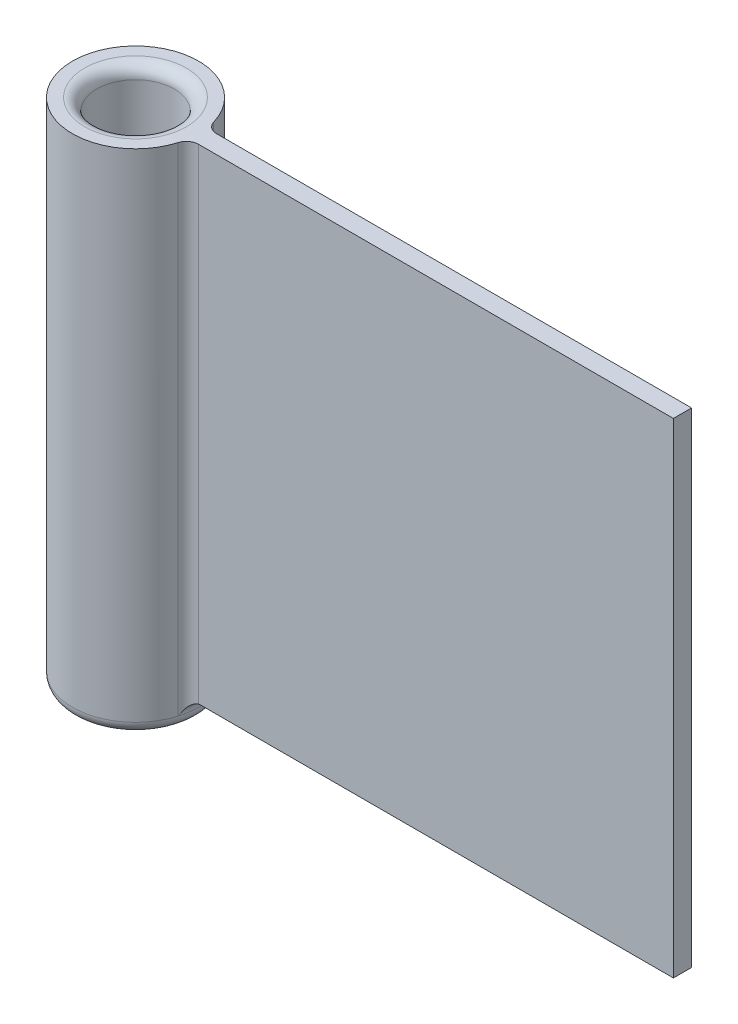
SolidWorks part; units mm, degrees
ref_plane "Front Plane" through (0, 0, 0) normal (0, 0, 1) x (1, 0, 0)
ref_plane "Top Plane" through (0, 0, 0) normal (0, 1, 0) x (1, 0, 0)
ref_plane "Right Plane" through (0, 0, 0) normal (1, 0, 0) x (0, 0, -1)
sketch "Sketch1" plane through (0, 0, 0) normal (0, 1, 0) x (1, 0, 0)
  circle A0 centre (0, 0) radius 3.2
  circle A1 centre (0, 0) radius 5.2
  dimension "D1" = 6.4
  dimension "D2" = 2
extrude "Boss-Extrude1" add sketch "Sketch1" along normal blind 40
sketch "Sketch3" plane through (0, 0, 0) normal (0, 1, 0) x (1, 0, 0)
  line L0 (0, 0) -> (55.2051, 0) construction
  line L1 (45.1456, 0.75) -> (5.1456, 0.75)
  line L2 (45.1456, -0.75) -> (5.1456, -0.75)
  line L3 (45.1456, -0.75) -> (45.1456, 0.75)
  line L4 (5.1456, -0.75) -> (5.1456, 0.75)
  circle A0 centre (0, 0) radius 5.2 construction
  dimension "D1" = 1.5
  dimension "D2" = 40
extrude "Boss-Extrude2" add sketch "Sketch3" along normal blind 40
sketch "Sketch4" plane through (0, 0, 0) normal (0, -1, 0) x (1, 0, 0)
  circle A0 centre (0, 0) radius 5.2
  dimension "D1" = 10.4
extrude "Boss-Extrude3" add sketch "Sketch4" along normal blind 2
fillet "Fillet1" radius 1 5 edges at (0, 0, 3.2) (0, 40, 3.2) (5.1456, 20, 0.75) (0, -2, -5.2) (5.1456, 20, -0.75)
fillet "Fillet2" radius 1 1 edges at (5.2, 0, 0)
